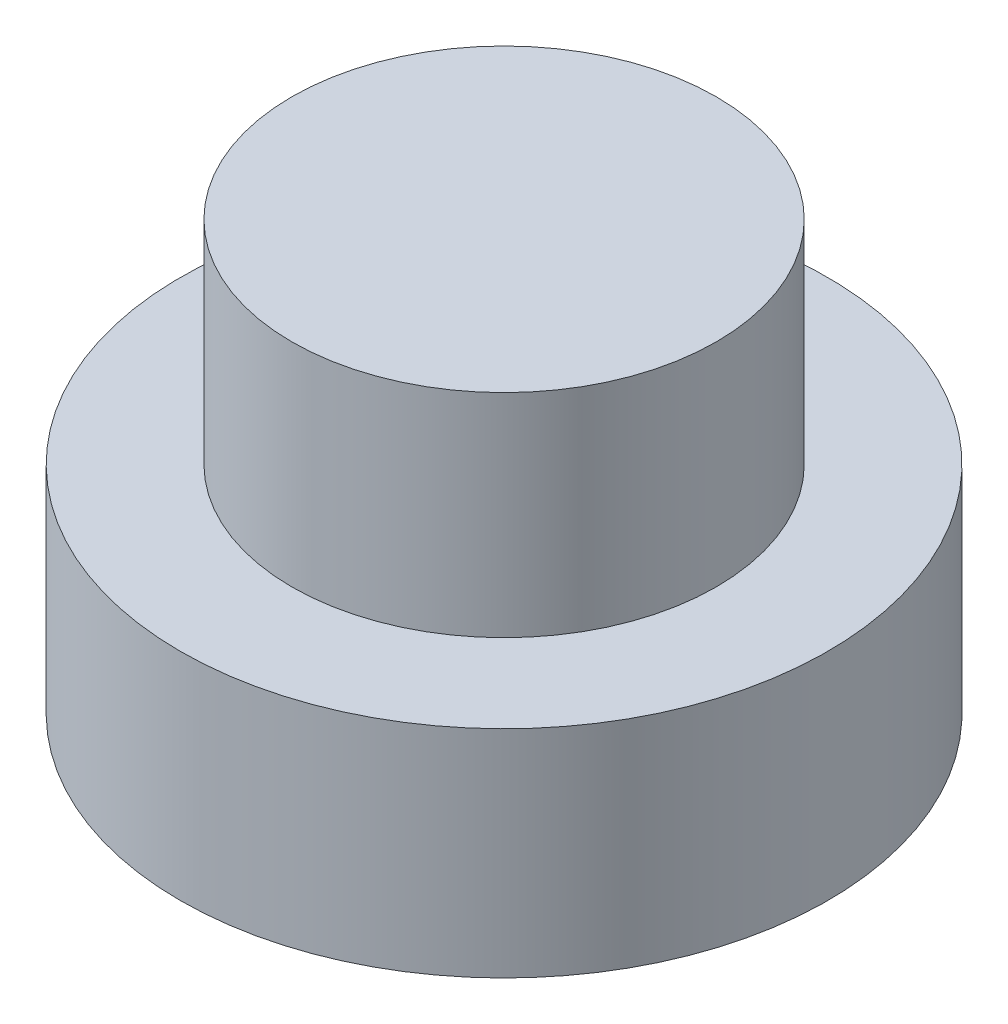
SolidWorks part; units mm, degrees
material "OMD-98"
ref_plane "Front Plane" through (0, 0, 0) normal (0, 0, 1) x (1, 0, 0)
ref_plane "Top Plane" through (0, 0, 0) normal (0, 1, 0) x (1, 0, 0)
ref_plane "Right Plane" through (0, 0, 0) normal (1, 0, 0) x (0, 0, -1)
sketch "Sketch1" plane through (0, 0, 0) normal (0, 1, 0) x (1, 0, 0)
  circle A0 centre (0, 0) radius 9
  dimension "D1" = 18
extrude "Boss-Extrude1" add sketch "Sketch1" along normal blind 6
sketch "Sketch2" plane through (0, 6, 0) normal (0, 1, 0) x (1, 0, 0)
  circle A0 centre (0, 0) radius 5.9
  dimension "D1" = 11.8
extrude "Boss-Extrude2" add sketch "Sketch2" along normal blind 20
sketch "Sketch5" plane through (0, 26, 0) normal (0, 1, 0) x (1, 0, 0)
  circle A0 centre (0, 0) radius 9.8378
extrude "Cut-Extrude3" cut sketch "Sketch5" against normal offset from surface (14.1 mm away) 5.9 up to face at (0, 6, 5.9)
